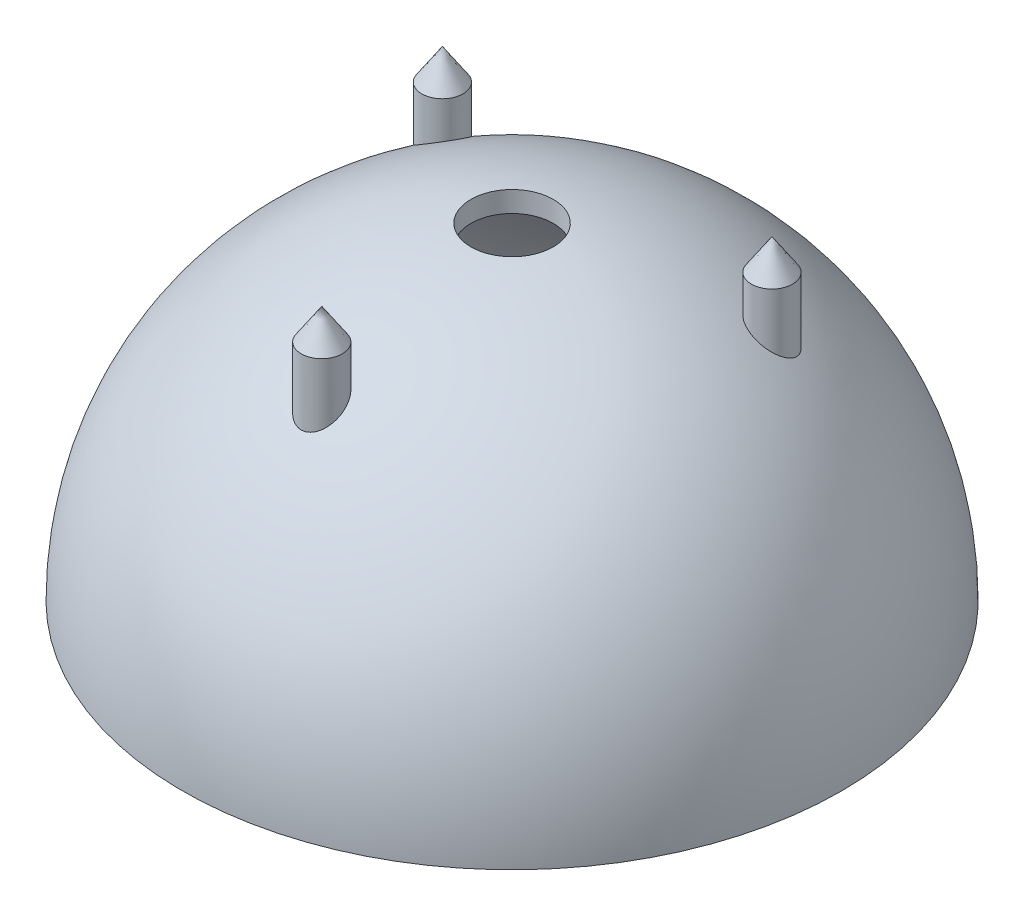
SolidWorks part; units mm, degrees
ref_plane "Front Plane" through (0, 0, 0) normal (0, 0, 1) x (1, 0, 0)
ref_plane "Top Plane" through (0, 0, 0) normal (0, 1, 0) x (1, 0, 0)
ref_plane "Right Plane" through (0, 0, 0) normal (1, 0, 0) x (0, 0, -1)
sketch "Sketch1" plane through (0, 0, 0) normal (0, 0, 1) x (1, 0, 0)
  line L0 (0, 0) -> (38.1, 0) construction
  line L1 (0, 38.1) -> (0, 0) construction
  line L2 (38.1, 0) -> (40.64, 0)
  line L3 (0, 38.1) -> (0, 40.64)
  arc A0 (0, 38.1) -> (38.1, 0) centre (0, 0) cw
  arc A1 (40.64, 0) -> (0, 40.64) centre (0, 0) ccw
  dimension "D1" = 38.1
  dimension "D2" = 2.54
revolve "Revolve1" add sketch "Sketch1" angle 360 about L3
ref_plane "Plane1" through (0, 39.37, 0) normal (0, -1, 0) x (1, 0, 0)
sketch "Sketch2" plane through (0, 39.37, 0) normal (0, -1, 0) x (1, 0, 0)
  line L1 (0, 23.4635) -> (20.32, -11.7318) construction
  line L2 (20.32, -11.7318) -> (-20.32, -11.7318) construction
  line L3 (-20.32, -11.7318) -> (0, 23.4635) construction
  line L4 (0, 0) -> (0, -11.7318) construction
  line L5 (0, 0) -> (10.16, 5.8659) construction
  line L6 (0, 0) -> (-10.16, 5.8659) construction
  circle A0 centre (0, 23.4635) radius 2.54
  circle A1 centre (-20.32, -11.7318) radius 2.54
  circle A2 centre (20.32, -11.7318) radius 2.54
  dimension "D2" = 5.08
  dimension "D1" = 40.64
extrude "Extrude1" add sketch "Sketch2" along normal up to surface (9.4598 mm away) up to face at (38.1, 0, 0)
sketch "Sketch4" plane through (0, 0, 0) normal (0, -1, 0) x (1, 0, 0)
  circle A0 centre (0, 0) radius 5.08
  dimension "D1" = 10.16
extrude "Extrude3" cut sketch "Sketch4" against normal through all
sketch "Sketch5" plane through (0, 0, 0) normal (1, 0, 0) x (0, 0, -1)
  line L0 (-20.9235, 39.37) -> (-23.4635, 43.18)
  line L1 (-20.9235, 39.37) -> (-23.4635, 39.37)
  line L2 (-20.9235, 39.37) -> (-26.0035, 39.37) construction
  line L3 (-23.4635, 39.37) -> (-23.4635, 43.18) construction
  line L4 (-23.4635, 43.18) -> (-23.4635, 39.37)
  dimension "D1" = 3.81
revolve "Revolve2" add sketch "Sketch5" angle 360 about L3
pattern_circular "CirPattern1" count 3 every 120 of "Revolve2"
